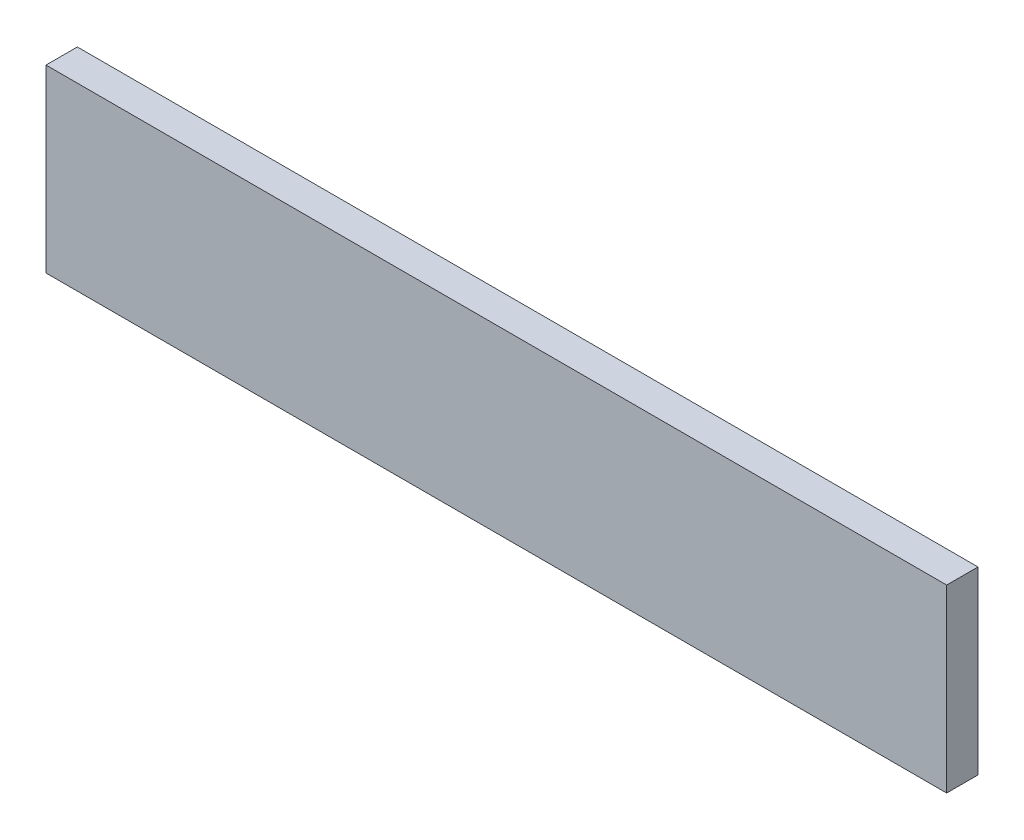
SolidWorks part; units mm, degrees
ref_plane "Ön Düzlem" through (0, 0, 0) normal (0, 0, 1) x (1, 0, 0)
ref_plane "Üst Düzlem" through (0, 0, 0) normal (0, 1, 0) x (1, 0, 0)
ref_plane "Sağ Düzlem" through (0, 0, 0) normal (1, 0, 0) x (0, 0, -1)
sketch "Çizim1" plane through (0, 0, 0) normal (0, 0, 1) x (1, 0, 0)
  line L1 (0, 0) -> (1150, 0)
  line L2 (0, 0) -> (0, -230)
  line L3 (0, -230) -> (1150, -230)
  line L4 (1150, 0) -> (1150, -230)
  dimension "D1" = 1150
  dimension "D2" = 230
base flange "Taban-Flanş1" sketch "Çizim1" thickness 40 reverse thickness direction no parameters "D1"=5
sketch "Büküm-Çizgileri1" [suppressed] plane through (0, 0, 0) normal (0, 1, 0) x (1, 0, 0)
sketch "Sınırlandırma-Kutusu1" [suppressed] plane through (0, 0, 0) normal (0, 1, 0) x (1, 0, 0)
sheet metal parameters "Sac-Levha1" thickness 40 parameters "D1"=5
flat pattern "Düz-Çoğaltma1" [suppressed]
sketch "Büküm-Çizgileri2" plane through (0, 0, 0) normal (0, 1, 0) x (1, 0, 0)
sketch3d "Sınırlandırma-Kutusu2" [suppressed]
  line L0 (0, -230, 0) -> (1150, -230, 0) construction
  line L1 (0, 0, 0) -> (1150, 0, 0) construction
  line L2 (0, -230, 0) -> (0, 0, 0) construction
  line L3 (1150, -230, 0) -> (1150, 0, 0) construction
